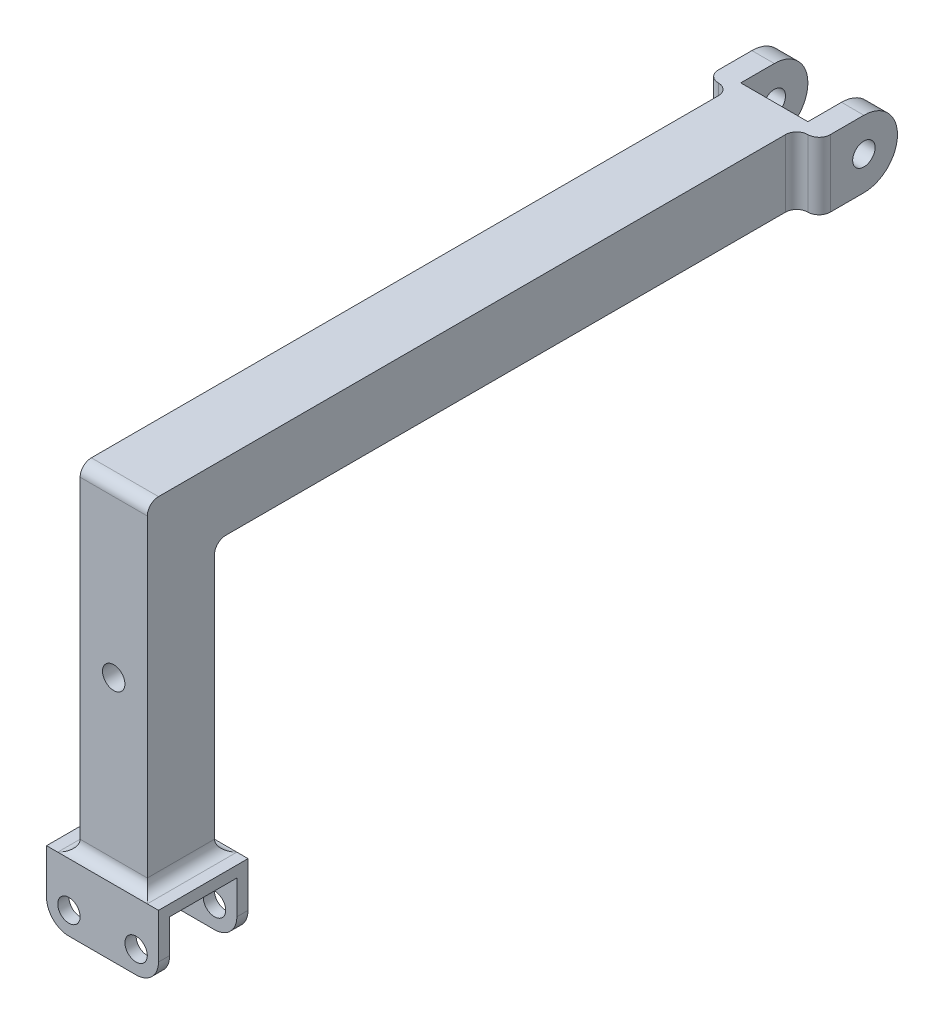
SolidWorks part; units mm, degrees
ref_plane "Front Plane" through (0, 0, 0) normal (0, 0, 1) x (1, 0, 0)
ref_plane "Top Plane" through (0, 0, 0) normal (0, 1, 0) x (1, 0, 0)
ref_plane "Right Plane" through (0, 0, 0) normal (1, 0, 0) x (0, 0, -1)
sketch "Sketch1" plane through (0, 0, 0) normal (1, 0, 0) x (0, 0, -1)
  line L0 (-1041.4698, 0) -> (1020.7234, 0) construction
  line L1 (-15, -10) -> (-15, 10) construction
  line L2 (-15, 15) -> (-15, 165)
  line L3 (20, -15) -> (15, -15)
  line L4 (20, -15) -> (20, 15)
  line L5 (20, 15) -> (15, 15)
  line L6 (-20, -15) -> (-20, 15)
  line L7 (15, -10) -> (15, 10) construction
  line L8 (-15, 10) -> (-15, -15)
  line L9 (-15, 165) -> (295, 165)
  line L10 (15, 10) -> (-15, 10)
  line L15 (15, -10) -> (-15, -10) construction
  line L16 (15, -15) -> (15, 10)
  line L17 (-15, -15) -> (-20, -15)
  line L18 (20, -15) -> (-20, -15) construction
  line L19 (0, -7.7188) -> (0, 70.1014) construction
  line L20 (15, 15) -> (15, 135)
  line L21 (15, 135) -> (295, 135)
  line L22 (295, 165) -> (295, 135) construction
  line L23 (0, 15) -> (-20, 15)
  line L24 (20, 15) -> (-20, 15) construction
  arc A0 (295, 135) -> (295, 165) centre (295, 150) ccw
  circle A1 centre (295, 150) radius 5
  point P5 (0, 0)
  point P11 (18.3333, -13.75)
  dimension "D1" = 40
  dimension "D2" = 30
  dimension "D4" = 15
  dimension "D5" = 150
  dimension "D6" = 310
  dimension "D3" = 5
  dimension "D7" = 30
extrude "Boss-Extrude1" add sketch "Sketch1" along normal blind 50 contours L21 A0 L9 L2 L23 L6 L17 L8 L10 L16 L3 L4 L5 L20 A1 region at (0, 90, 11.241)
sketch "Sketch2" plane through (0, 165, 0) normal (0, 1, 0) x (1, 0, 0)
  line L0 (50, 310) -> (0, 310) construction
  line L1 (10, 310) -> (40, 310)
  line L2 (10, 310) -> (10, 280)
  line L3 (10, 280) -> (40, 280)
  line L4 (40, 310) -> (40, 280)
  line L5 (0, -15) -> (0, 295) construction
  line L6 (50, -15) -> (0, -15) construction
  line L7 (0, 275) -> (5, 275)
  line L8 (0, 275) -> (0, -15)
  line L9 (0, -15) -> (10, -15)
  line L10 (10, 270) -> (10, -15)
  line L12 (50, -15) -> (40, -15)
  line L13 (50, -15) -> (50, 275)
  line L14 (50, 275) -> (45, 275)
  line L15 (40, -15) -> (40, 270)
  arc A0 (40, 270) -> (45, 275) centre (45, 270) cw
  arc A1 (10, 270) -> (5, 275) centre (5, 270) ccw
  point P21 (40, 275)
  point P24 (10, 275)
  dimension "D6" = 5
  dimension "D1" = 30
  dimension "D2" = 30
  dimension "D3" = 10
  dimension "D4" = 290
  dimension "D5" = 290
extrude "Cut-Extrude1" cut sketch "Sketch2" against normal blind 150
sketch "Sketch3" plane through (0, 0, 20) normal (0, 0, 1) x (1, 0, 0)
  line L0 (50, -15) -> (50, 15) construction
  line L1 (10, -15) -> (40, -15)
  line L2 (0, -5) -> (0, 5)
  line L3 (0, 5) -> (50, 5)
  line L4 (50, -5) -> (50, 5)
  circle A0 centre (10, -5) radius 5
  circle A1 centre (40, -5) radius 5
  arc A2 (40, -15) -> (50, -5) centre (40, -5) ccw
  arc A3 (10, -15) -> (0, -5) centre (10, -5) cw
  point P15 (0, -15)
  dimension "D2" = 30
  dimension "D3" = 10
  dimension "D4" = 10
  dimension "D1" = 20
extrude "Cut-Extrude2" cut sketch "Sketch3" against normal through all contours A0 | A1
fillet "Fillet1" radius 10 4 edges at (50, -15, -17.5) (50, -15, 17.5) (0, -15, -17.5) (0, -15, 17.5)
fillet "Fillet2" radius 5 6 edges at (25, 135, -15) (10, 15, 0) (25, 15, 15) (25, 15, -15) (40, 15, 0) (25, 165, 15)
fillet "Fillet3" radius 5 2 edges at (0, 150, -275) (50, 150, -275)
sketch "Sketch4" plane through (0, 0, 15) normal (0, 0, 1) x (1, 0, 0)
  line L0 (25, 160) -> (25, 20) construction
  line L1 (40, 160) -> (10, 160) construction
  line L2 (10, 20) -> (40, 20) construction
  circle A0 centre (25, 90) radius 5
extrude "Cut-Extrude3" cut sketch "Sketch4" against normal blind 150
